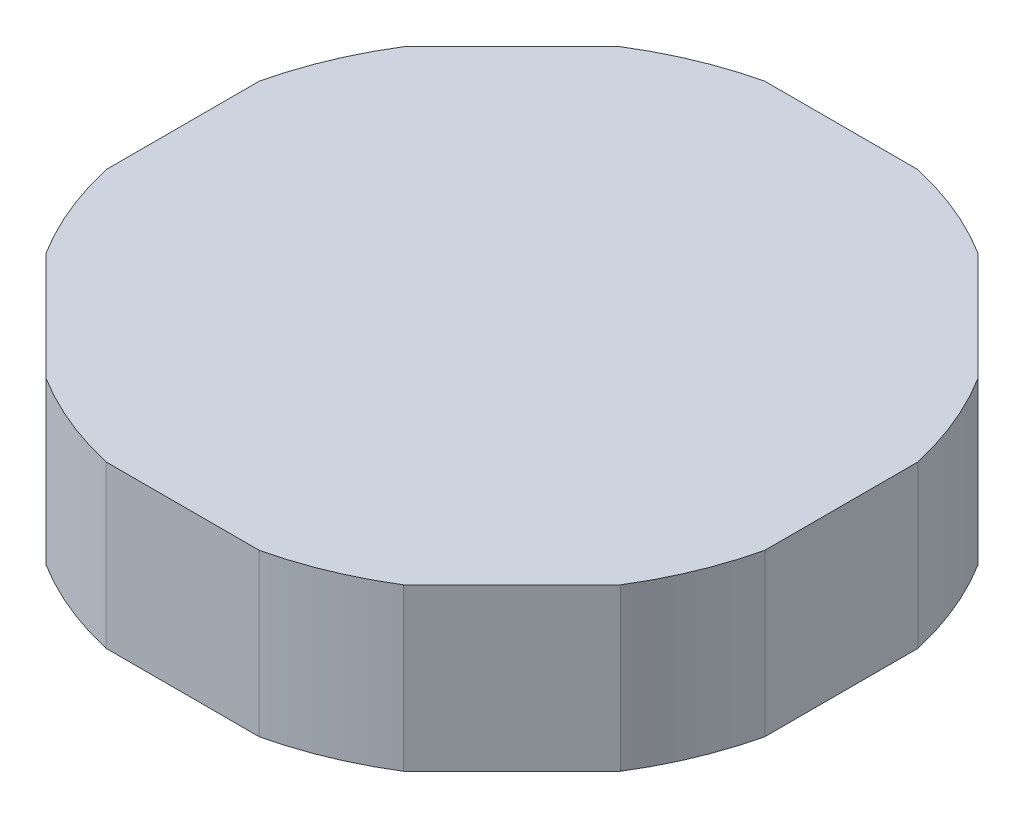
SolidWorks part; units mm, degrees
ref_plane "Front Plane" through (0, 0, 0) normal (0, 0, 1) x (1, 0, 0)
ref_plane "Top Plane" through (0, 0, 0) normal (0, 1, 0) x (1, 0, 0)
ref_plane "Right Plane" through (0, 0, 0) normal (1, 0, 0) x (0, 0, -1)
sketch "Sketch1" plane through (0, 0, 0) normal (0, 1, 0) x (1, 0, 0)
  line L0 (6.1213, 1.425) -> (6.1213, -1.425) construction
  line L1 (26, -1.425) -> (26, 1.425) construction
  circle A0 centre (0, 0) radius 6.285
extrude "Boss-Extrude1" add sketch "Sketch1" along normal blind 3
sketch "Sketch2" plane through (0, 3, 0) normal (0, 1, 0) x (1, 0, 0)
  line L0 (6.1213, 1.425) -> (6.1213, -1.425) construction
  line L1 (6.1213, -2.5355) -> (6.1213, 2.5355)
  line L2 (6.1213, 2.5355) -> (2.5355, 6.1213)
  line L3 (2.5355, 6.1213) -> (-2.5355, 6.1213)
  line L4 (-2.5355, 6.1213) -> (-6.1213, 2.5355)
  line L5 (-6.1213, 2.5355) -> (-6.1213, -2.5355)
  line L6 (-6.1213, -2.5355) -> (-2.5355, -6.1213)
  line L7 (-2.5355, -6.1213) -> (2.5355, -6.1213)
  line L8 (2.5355, -6.1213) -> (6.1213, -2.5355)
  circle A0 centre (0, 0) radius 6.1213 construction
  circle A1 centre (0, 0) radius 8.1213
  dimension "D1" = 2
extrude "Cut-Extrude1" cut sketch "Sketch2" against normal through all
